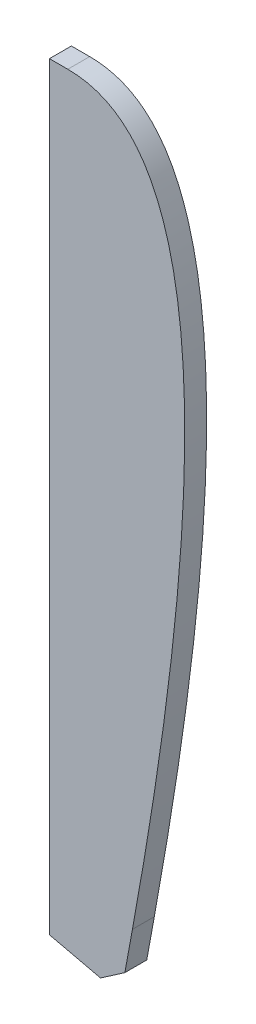
SolidWorks part; units mm, degrees
material "MDF"
ref_plane "Front Plane" through (0, 0, 0) normal (0, 0, 1) x (1, 0, 0)
ref_plane "Top Plane" through (0, 0, 0) normal (0, 1, 0) x (1, 0, 0)
ref_plane "Right Plane" through (0, 0, 0) normal (1, 0, 0) x (0, 0, -1)
sketch "Sketch2" plane through (0, 0, 0) normal (0, 0, 1) x (1, 0, 0)
  line L0 (12.7, -5464.9635) -> (54.1406, -5474.5946)
  line L1 (12.7, -5024.8784) -> (12.7, -5142.5528) construction
  line L2 (48.0775, -5473.1855) -> (326.4096, -5537.8717) construction
  line L3 (12.7, -5464.9635) -> (12.7, -5024.8784)
  line L4 (54.1406, -5474.5946) -> (136.525, -5024.8784)
  line L5 (136.525, -5024.8784) -> (12.7, -5024.8784)
  dimension "D1" = 457.2
  dimension "D2" = 42.545
  dimension "D3" = 123.825
extrude "Boss-Extrude1" add sketch "Sketch2" against normal blind 12.7
fillet "Fillet1" radius 406.4 1 edges at (136.525, -5024.8784, -6.35)
chamfer "Chamfer1" distance 12.7 angle 45 1 edges at (54.1406, -5474.5946, -6.35)
